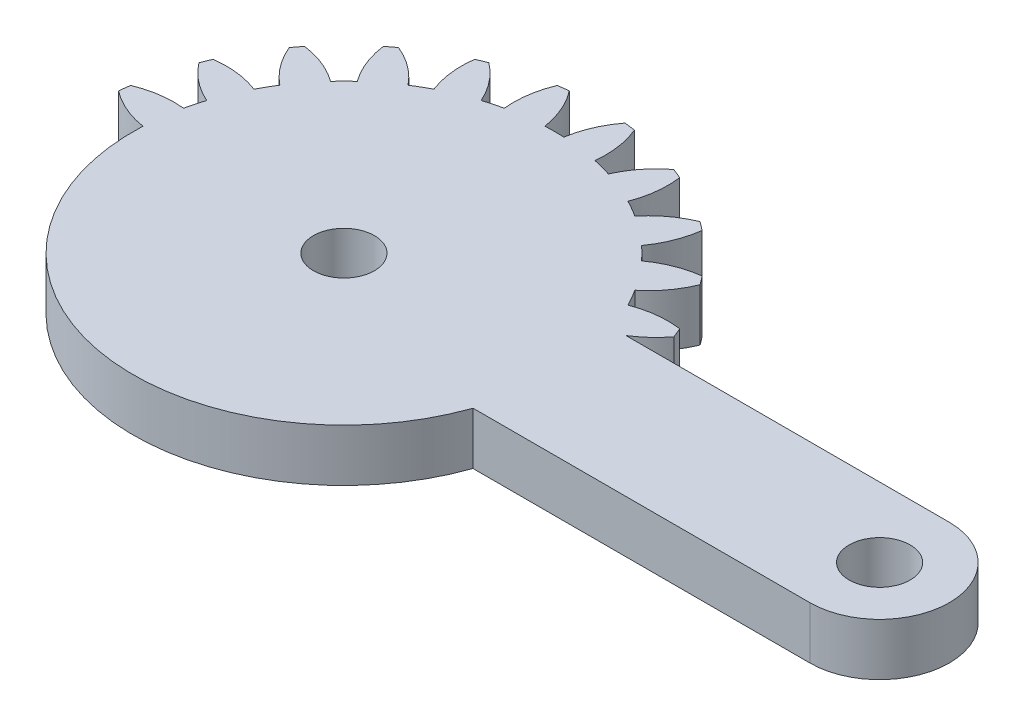
SolidWorks part; units mm, degrees
ref_plane "Front Plane" through (0, 0, 0) normal (0, 0, 1) x (1, 0, 0)
ref_plane "Top Plane" through (0, 0, 0) normal (0, 1, 0) x (1, 0, 0)
ref_plane "Right Plane" through (0, 0, 0) normal (1, 0, 0) x (0, 0, -1)
sketch "Sketch1" plane through (0, 0, 0) normal (0, 1, 0) x (1, 0, 0)
  line L0 (20.6437, 4) -> (2.0816, 4)
  line L1 (2.0816, -4) -> (20.6437, -4)
  arc A0 (2.0816, 4) -> (3.5217, 5.3071) centre (-0.7683, 8.5867) ccw
  arc A1 (3.5217, 5.3071) -> (3.2829, 5.8838) centre (-10.1063, 0) ccw
  arc A2 (3.2829, 5.8838) -> (0.6271, 5.5703) centre (2.5684, 0.5313) ccw
  arc A3 (0.6271, 5.5703) -> (0.0844, 6.5103) centre (-10.1063, 0) ccw
  arc A4 (0.0844, 6.5103) -> (1.6838, 8.6535) centre (-3.3089, 10.711) ccw
  arc A5 (1.6838, 8.6535) -> (1.3038, 9.1487) centre (-10.1063, 0) ccw
  arc A6 (1.3038, 9.1487) -> (-1.1803, 8.1585) centre (1.999, 3.7936) ccw
  arc A7 (-1.1803, 8.1585) -> (-1.9479, 8.926) centre (-10.1063, 0) ccw
  arc A8 (-1.9479, 8.926) -> (-0.9576, 11.4102) centre (-6.3127, 12.1053) ccw
  arc A9 (-0.9576, 11.4102) -> (-1.4528, 11.7901) centre (-10.1063, 0) ccw
  arc A10 (-1.4528, 11.7901) -> (-3.596, 10.1907) centre (0.6046, 6.7975) ccw
  arc A11 (-3.596, 10.1907) -> (-4.5361, 10.7334) centre (-10.1063, 0) ccw
  arc A12 (-4.5361, 10.7334) -> (-4.2225, 13.3892) centre (-9.5751, 12.6747) ccw
  arc A13 (-4.2225, 13.3892) -> (-4.7992, 13.6281) centre (-10.1063, 0) ccw
  arc A14 (-4.7992, 13.6281) -> (-6.4554, 11.5285) centre (-1.5196, 9.3381) ccw
  arc A15 (-6.4554, 11.5285) -> (-7.5039, 11.8094) centre (-10.1063, 0) ccw
  arc A16 (-7.5039, 11.8094) -> (-7.8884, 14.4558) centre (-12.8736, 12.3803) ccw
  arc A17 (-7.8884, 14.4558) -> (-8.5072, 14.5373) centre (-10.1063, 0) ccw
  arc A18 (-8.5072, 14.5373) -> (-9.5636, 12.0806) centre (-4.2291, 11.2423) ccw
  arc A19 (-9.5636, 12.0806) -> (-10.6491, 12.0806) centre (-10.1063, 0) ccw
  arc A20 (-10.6491, 12.0806) -> (-11.7054, 14.5373) centre (-15.9836, 11.2423) ccw
  arc A21 (-11.7054, 14.5373) -> (-12.3243, 14.4558) centre (-10.1063, 0) ccw
  arc A22 (-12.3243, 14.4558) -> (-12.7088, 11.8094) centre (-7.3391, 12.3803) ccw
  arc A23 (-12.7088, 11.8094) -> (-13.7573, 11.5285) centre (-10.1063, 0) ccw
  arc A24 (-13.7573, 11.5285) -> (-15.4135, 13.6281) centre (-18.6931, 9.3381) ccw
  arc A25 (-15.4135, 13.6281) -> (-15.9901, 13.3892) centre (-10.1063, 0) ccw
  arc A26 (-15.9901, 13.3892) -> (-15.6766, 10.7334) centre (-10.6376, 12.6747) ccw
  arc A27 (-15.6766, 10.7334) -> (-16.6166, 10.1907) centre (-10.1063, 0) ccw
  arc A28 (-16.6166, 10.1907) -> (-18.7599, 11.7901) centre (-20.8173, 6.7975) ccw
  arc A29 (-18.7599, 11.7901) -> (-19.255, 11.4102) centre (-10.1063, 0) ccw
  arc A30 (-19.255, 11.4102) -> (-18.2648, 8.926) centre (-13.9, 12.1053) ccw
  arc A31 (-18.2648, 8.926) -> (-19.0324, 8.1585) centre (-10.1063, 0) ccw
  arc A32 (-19.0324, 8.1585) -> (-21.5165, 9.1487) centre (-22.2117, 3.7936) ccw
  arc A33 (-21.5165, 9.1487) -> (-21.8965, 8.6535) centre (-10.1063, 0) ccw
  arc A34 (-21.8965, 8.6535) -> (-20.2971, 6.5103) centre (-16.9038, 10.711) ccw
  arc A35 (-20.2971, 6.5103) -> (-20.8398, 5.5703) centre (-10.1063, 0) ccw
  arc A36 (-20.8398, 5.5703) -> (-23.4956, 5.8838) centre (-22.7811, 0.5313) ccw
  arc A37 (-23.4956, 5.8838) -> (-23.7344, 5.3071) centre (-10.1063, 0) ccw
  arc A38 (-23.7344, 5.3071) -> (-21.6348, 3.6509) centre (-19.4444, 8.5867) ccw
  arc A39 (-21.6348, 3.6509) -> (-21.9157, 2.6025) centre (-10.1063, 0) ccw
  arc A40 (-21.9157, 2.6025) -> (-24.5622, 2.2179) centre (-22.4867, -2.7673) ccw
  arc A41 (-24.5622, 2.2179) -> (-24.6437, 1.5991) centre (-10.1063, 0) ccw
  arc A42 (-24.6437, 1.5991) -> (-22.1869, 0.5427) centre (-21.3486, 5.8773) ccw
  arc A43 (-22.1869, 0.5427) -> (-22.1869, -0.5427) centre (-10.1063, 0) ccw
  arc A44 (-22.1869, -0.5427) -> (-24.6437, -1.5991) centre (-21.3486, -5.8773) ccw
  arc A45 (-24.6437, -1.5991) -> (-24.5622, -2.2179) centre (-10.1063, 0) ccw
  arc A46 (-24.5622, -2.2179) -> (-21.9157, -2.6025) centre (-22.4867, 2.7673) ccw
  arc A47 (-21.9157, -2.6025) -> (-21.6348, -3.6509) centre (-10.1063, 0) ccw
  arc A48 (-21.6348, -3.6509) -> (-23.7344, -5.3071) centre (-19.4444, -8.5867) ccw
  arc A49 (-23.7344, -5.3071) -> (-23.4956, -5.8838) centre (-10.1063, 0) ccw
  arc A50 (-23.4956, -5.8838) -> (-20.8398, -5.5703) centre (-22.7811, -0.5313) ccw
  arc A51 (-20.8398, -5.5703) -> (-20.2971, -6.5103) centre (-10.1063, 0) ccw
  arc A52 (-20.2971, -6.5103) -> (-21.8965, -8.6535) centre (-16.9038, -10.711) ccw
  arc A53 (-21.8965, -8.6535) -> (-21.5165, -9.1487) centre (-10.1063, 0) ccw
  arc A54 (-21.5165, -9.1487) -> (-19.0324, -8.1585) centre (-22.2117, -3.7936) ccw
  arc A55 (-19.0324, -8.1585) -> (-18.2648, -8.926) centre (-10.1063, 0) ccw
  arc A56 (-18.2648, -8.926) -> (-19.255, -11.4102) centre (-13.9, -12.1053) ccw
  arc A57 (-19.255, -11.4102) -> (-18.7599, -11.7901) centre (-10.1063, 0) ccw
  arc A58 (-18.7599, -11.7901) -> (-16.6166, -10.1907) centre (-20.8173, -6.7975) ccw
  arc A59 (-16.6166, -10.1907) -> (-15.6766, -10.7334) centre (-10.1063, 0) ccw
  arc A60 (-15.6766, -10.7334) -> (-15.9901, -13.3892) centre (-10.6376, -12.6747) ccw
  arc A61 (-15.9901, -13.3892) -> (-15.4135, -13.6281) centre (-10.1063, 0) ccw
  arc A62 (-15.4135, -13.6281) -> (-13.7573, -11.5285) centre (-18.6931, -9.3381) ccw
  arc A63 (-13.7573, -11.5285) -> (-12.7088, -11.8094) centre (-10.1063, 0) ccw
  arc A64 (-12.7088, -11.8094) -> (-12.3243, -14.4558) centre (-7.3391, -12.3803) ccw
  arc A65 (-12.3243, -14.4558) -> (-11.7054, -14.5373) centre (-10.1063, 0) ccw
  arc A66 (-11.7054, -14.5373) -> (-10.6491, -12.0806) centre (-15.9836, -11.2423) ccw
  arc A67 (-10.6491, -12.0806) -> (-9.5636, -12.0806) centre (-10.1063, 0) ccw
  arc A68 (-9.5636, -12.0806) -> (-8.5072, -14.5373) centre (-4.2291, -11.2423) ccw
  arc A69 (-8.5072, -14.5373) -> (-7.8884, -14.4558) centre (-10.1063, 0) ccw
  arc A70 (-7.8884, -14.4558) -> (-7.5039, -11.8094) centre (-12.8736, -12.3803) ccw
  arc A71 (-7.5039, -11.8094) -> (-6.4554, -11.5285) centre (-10.1063, 0) ccw
  arc A72 (-6.4554, -11.5285) -> (-4.7992, -13.6281) centre (-1.5196, -9.3381) ccw
  arc A73 (-4.7992, -13.6281) -> (-4.2225, -13.3892) centre (-10.1063, 0) ccw
  arc A74 (-4.2225, -13.3892) -> (-4.5361, -10.7334) centre (-9.5751, -12.6747) ccw
  arc A75 (-4.5361, -10.7334) -> (-3.596, -10.1907) centre (-10.1063, 0) ccw
  arc A76 (-3.596, -10.1907) -> (-1.4528, -11.7901) centre (0.6046, -6.7975) ccw
  arc A77 (-1.4528, -11.7901) -> (-0.9576, -11.4102) centre (-10.1063, 0) ccw
  arc A78 (-0.9576, -11.4102) -> (-1.9479, -8.926) centre (-6.3127, -12.1053) ccw
  arc A79 (-1.9479, -8.926) -> (-1.1803, -8.1585) centre (-10.1063, 0) ccw
  arc A80 (-1.1803, -8.1585) -> (1.3038, -9.1487) centre (1.999, -3.7936) ccw
  arc A81 (1.3038, -9.1487) -> (1.6838, -8.6535) centre (-10.1063, 0) ccw
  arc A82 (1.6838, -8.6535) -> (0.0844, -6.5103) centre (-3.3089, -10.711) ccw
  arc A83 (0.0844, -6.5103) -> (0.6271, -5.5703) centre (-10.1063, 0) ccw
  arc A84 (0.6271, -5.5703) -> (3.2829, -5.8838) centre (2.5684, -0.5313) ccw
  arc A85 (3.2829, -5.8838) -> (3.5217, -5.3071) centre (-10.1063, 0) ccw
  arc A86 (3.5217, -5.3071) -> (2.0816, -4) centre (-0.7683, -8.5867) ccw
  arc A87 (20.6437, -4) -> (20.6437, 4) centre (20.6437, 0) ccw
  circle A88 centre (-10.1063, 0) radius 1.75
  circle A89 centre (20.6437, 0) radius 1.75
  dimension "D1" = 3.5
  dimension "D2" = 3.5
extrude "Boss-Extrude1" add sketch "Sketch1" along normal blind 3
sketch "Sketch2" plane through (0, 3, 0) normal (0, 1, 0) x (1, 0, 0)
  line L0 (2.0816, -4) -> (1.3057, -4)
  line L2 (20.6437, 4) -> (2.0816, 4)
  line L3 (2.0816, -4) -> (20.6437, -4)
  line L4 (20.6437, 4) -> (2.0816, 4)
  line L5 (2.0816, -4) -> (20.6437, -4)
  circle A0 centre (-10.1063, 0) radius 12.0927
  arc A88 (20.6437, -4) -> (20.6437, 4) centre (20.6437, 0) ccw
  arc A89 (2.0816, 4) -> (3.5217, 5.3071) centre (-0.7683, 8.5867) ccw
  arc A90 (3.5217, 5.3071) -> (3.2829, 5.8838) centre (-10.1063, 0) ccw
  arc A91 (3.2829, 5.8838) -> (0.6271, 5.5703) centre (2.5684, 0.5313) ccw
  arc A92 (0.6271, 5.5703) -> (0.0844, 6.5103) centre (-10.1063, 0) ccw
  arc A93 (0.0844, 6.5103) -> (1.6838, 8.6535) centre (-3.3089, 10.711) ccw
  arc A94 (1.6838, 8.6535) -> (1.3038, 9.1487) centre (-10.1063, 0) ccw
  arc A95 (1.3038, 9.1487) -> (-1.1803, 8.1585) centre (1.999, 3.7936) ccw
  arc A96 (-1.1803, 8.1585) -> (-1.9479, 8.926) centre (-10.1063, 0) ccw
  arc A97 (-1.9479, 8.926) -> (-0.9576, 11.4102) centre (-6.3127, 12.1053) ccw
  arc A98 (-0.9576, 11.4102) -> (-1.4528, 11.7901) centre (-10.1063, 0) ccw
  arc A99 (-1.4528, 11.7901) -> (-3.596, 10.1907) centre (0.6046, 6.7975) ccw
  arc A100 (-3.596, 10.1907) -> (-4.5361, 10.7334) centre (-10.1063, 0) ccw
  arc A101 (-4.5361, 10.7334) -> (-4.2225, 13.3892) centre (-9.5751, 12.6747) ccw
  arc A102 (-4.2225, 13.3892) -> (-4.7992, 13.6281) centre (-10.1063, 0) ccw
  arc A103 (-4.7992, 13.6281) -> (-6.4554, 11.5285) centre (-1.5196, 9.3381) ccw
  arc A104 (-6.4554, 11.5285) -> (-7.5039, 11.8094) centre (-10.1063, 0) ccw
  arc A105 (-7.5039, 11.8094) -> (-7.8884, 14.4558) centre (-12.8736, 12.3803) ccw
  arc A106 (-7.8884, 14.4558) -> (-8.5072, 14.5373) centre (-10.1063, 0) ccw
  arc A107 (-8.5072, 14.5373) -> (-9.5636, 12.0806) centre (-4.2291, 11.2423) ccw
  arc A108 (-9.5636, 12.0806) -> (-10.6491, 12.0806) centre (-10.1063, 0) ccw
  arc A109 (-10.6491, 12.0806) -> (-11.7054, 14.5373) centre (-15.9836, 11.2423) ccw
  arc A110 (-11.7054, 14.5373) -> (-12.3243, 14.4558) centre (-10.1063, 0) ccw
  arc A111 (-12.3243, 14.4558) -> (-12.7088, 11.8094) centre (-7.3391, 12.3803) ccw
  arc A112 (-12.7088, 11.8094) -> (-13.7573, 11.5285) centre (-10.1063, 0) ccw
  arc A113 (-13.7573, 11.5285) -> (-15.4135, 13.6281) centre (-18.6931, 9.3381) ccw
  arc A114 (-15.4135, 13.6281) -> (-15.9901, 13.3892) centre (-10.1063, 0) ccw
  arc A115 (-15.9901, 13.3892) -> (-15.6766, 10.7334) centre (-10.6376, 12.6747) ccw
  arc A116 (-15.6766, 10.7334) -> (-16.6166, 10.1907) centre (-10.1063, 0) ccw
  arc A117 (-16.6166, 10.1907) -> (-18.7599, 11.7901) centre (-20.8173, 6.7975) ccw
  arc A118 (-18.7599, 11.7901) -> (-19.255, 11.4102) centre (-10.1063, 0) ccw
  arc A119 (-19.255, 11.4102) -> (-18.2648, 8.926) centre (-13.9, 12.1053) ccw
  arc A120 (-18.2648, 8.926) -> (-19.0324, 8.1585) centre (-10.1063, 0) ccw
  arc A121 (-19.0324, 8.1585) -> (-21.5165, 9.1487) centre (-22.2117, 3.7936) ccw
  arc A122 (-21.5165, 9.1487) -> (-21.8965, 8.6535) centre (-10.1063, 0) ccw
  arc A123 (-21.8965, 8.6535) -> (-20.2971, 6.5103) centre (-16.9038, 10.711) ccw
  arc A124 (-20.2971, 6.5103) -> (-20.8398, 5.5703) centre (-10.1063, 0) ccw
  arc A125 (-20.8398, 5.5703) -> (-23.4956, 5.8838) centre (-22.7811, 0.5313) ccw
  arc A126 (-23.4956, 5.8838) -> (-23.7344, 5.3071) centre (-10.1063, 0) ccw
  arc A127 (-23.7344, 5.3071) -> (-21.6348, 3.6509) centre (-19.4444, 8.5867) ccw
  arc A128 (-21.6348, 3.6509) -> (-21.9157, 2.6025) centre (-10.1063, 0) ccw
  arc A129 (-21.9157, 2.6025) -> (-24.5622, 2.2179) centre (-22.4867, -2.7673) ccw
  arc A130 (-24.5622, 2.2179) -> (-24.6437, 1.5991) centre (-10.1063, 0) ccw
  arc A131 (-24.6437, 1.5991) -> (-22.1869, 0.5427) centre (-21.3486, 5.8773) ccw
  arc A132 (-22.1869, 0.5427) -> (-22.1869, -0.5427) centre (-10.1063, 0) ccw
  arc A133 (-22.1869, -0.5427) -> (-24.6437, -1.5991) centre (-21.3486, -5.8773) ccw
  arc A134 (-24.6437, -1.5991) -> (-24.5622, -2.2179) centre (-10.1063, 0) ccw
  arc A135 (-24.5622, -2.2179) -> (-21.9157, -2.6025) centre (-22.4867, 2.7673) ccw
  arc A136 (-21.9157, -2.6025) -> (-21.6348, -3.6509) centre (-10.1063, 0) ccw
  arc A137 (-21.6348, -3.6509) -> (-23.7344, -5.3071) centre (-19.4444, -8.5867) ccw
  arc A138 (-23.7344, -5.3071) -> (-23.4956, -5.8838) centre (-10.1063, 0) ccw
  arc A139 (-23.4956, -5.8838) -> (-20.8398, -5.5703) centre (-22.7811, -0.5313) ccw
  arc A140 (-20.8398, -5.5703) -> (-20.2971, -6.5103) centre (-10.1063, 0) ccw
  arc A141 (-20.2971, -6.5103) -> (-21.8965, -8.6535) centre (-16.9038, -10.711) ccw
  arc A142 (-21.8965, -8.6535) -> (-21.5165, -9.1487) centre (-10.1063, 0) ccw
  arc A143 (-21.5165, -9.1487) -> (-19.0324, -8.1585) centre (-22.2117, -3.7936) ccw
  arc A144 (-19.0324, -8.1585) -> (-18.2648, -8.926) centre (-10.1063, 0) ccw
  arc A145 (-18.2648, -8.926) -> (-19.255, -11.4102) centre (-13.9, -12.1053) ccw
  arc A146 (-19.255, -11.4102) -> (-18.7599, -11.7901) centre (-10.1063, 0) ccw
  arc A147 (-18.7599, -11.7901) -> (-16.6166, -10.1907) centre (-20.8173, -6.7975) ccw
  arc A148 (-16.6166, -10.1907) -> (-15.6766, -10.7334) centre (-10.1063, 0) ccw
  arc A149 (-15.6766, -10.7334) -> (-15.9901, -13.3892) centre (-10.6376, -12.6747) ccw
  arc A150 (-15.9901, -13.3892) -> (-15.4135, -13.6281) centre (-10.1063, 0) ccw
  arc A151 (-15.4135, -13.6281) -> (-13.7573, -11.5285) centre (-18.6931, -9.3381) ccw
  arc A152 (-13.7573, -11.5285) -> (-12.7088, -11.8094) centre (-10.1063, 0) ccw
  arc A153 (-12.7088, -11.8094) -> (-12.3243, -14.4558) centre (-7.3391, -12.3803) ccw
  arc A154 (-12.3243, -14.4558) -> (-11.7054, -14.5373) centre (-10.1063, 0) ccw
  arc A155 (-11.7054, -14.5373) -> (-10.6491, -12.0806) centre (-15.9836, -11.2423) ccw
  arc A156 (-10.6491, -12.0806) -> (-9.5636, -12.0806) centre (-10.1063, 0) ccw
  arc A157 (-9.5636, -12.0806) -> (-8.5072, -14.5373) centre (-4.2291, -11.2423) ccw
  arc A158 (-8.5072, -14.5373) -> (-7.8884, -14.4558) centre (-10.1063, 0) ccw
  arc A159 (-7.8884, -14.4558) -> (-7.5039, -11.8094) centre (-12.8736, -12.3803) ccw
  arc A160 (-7.5039, -11.8094) -> (-6.4554, -11.5285) centre (-10.1063, 0) ccw
  arc A161 (-6.4554, -11.5285) -> (-4.7992, -13.6281) centre (-1.5196, -9.3381) ccw
  arc A162 (-4.7992, -13.6281) -> (-4.2225, -13.3892) centre (-10.1063, 0) ccw
  arc A163 (-4.2225, -13.3892) -> (-4.5361, -10.7334) centre (-9.5751, -12.6747) ccw
  arc A164 (-4.5361, -10.7334) -> (-3.596, -10.1907) centre (-10.1063, 0) ccw
  arc A165 (-3.596, -10.1907) -> (-1.4528, -11.7901) centre (0.6046, -6.7975) ccw
  arc A166 (-1.4528, -11.7901) -> (-0.9576, -11.4102) centre (-10.1063, 0) ccw
  arc A167 (-0.9576, -11.4102) -> (-1.9479, -8.926) centre (-6.3127, -12.1053) ccw
  arc A168 (-1.9479, -8.926) -> (-1.1803, -8.1585) centre (-10.1063, 0) ccw
  arc A169 (-1.1803, -8.1585) -> (1.3038, -9.1487) centre (1.999, -3.7936) ccw
  arc A170 (1.3038, -9.1487) -> (1.6838, -8.6535) centre (-10.1063, 0) ccw
  arc A171 (1.6838, -8.6535) -> (0.0844, -6.5103) centre (-3.3089, -10.711) ccw
  arc A172 (0.0844, -6.5103) -> (0.6271, -5.5703) centre (-10.1063, 0) ccw
  arc A173 (0.6271, -5.5703) -> (3.2829, -5.8838) centre (2.5684, -0.5313) ccw
  arc A174 (3.2829, -5.8838) -> (3.5217, -5.3071) centre (-10.1063, 0) ccw
  arc A175 (3.5217, -5.3071) -> (2.0816, -4) centre (-0.7683, -8.5867) ccw
  arc A176 (20.6437, -4) -> (20.6437, 4) centre (20.6437, 0) ccw
  arc A177 (2.0816, 4) -> (3.5217, 5.3071) centre (-0.7683, 8.5867) ccw
  arc A178 (3.5217, 5.3071) -> (3.2829, 5.8838) centre (-10.1063, 0) ccw
  arc A179 (3.2829, 5.8838) -> (0.6271, 5.5703) centre (2.5684, 0.5313) ccw
  arc A180 (0.6271, 5.5703) -> (0.0844, 6.5103) centre (-10.1063, 0) ccw
  arc A181 (0.0844, 6.5103) -> (1.6838, 8.6535) centre (-3.3089, 10.711) ccw
  arc A182 (1.6838, 8.6535) -> (1.3038, 9.1487) centre (-10.1063, 0) ccw
  arc A183 (1.3038, 9.1487) -> (-1.1803, 8.1585) centre (1.999, 3.7936) ccw
  arc A184 (-1.1803, 8.1585) -> (-1.9479, 8.926) centre (-10.1063, 0) ccw
  arc A185 (-1.9479, 8.926) -> (-0.9576, 11.4102) centre (-6.3127, 12.1053) ccw
  arc A186 (-0.9576, 11.4102) -> (-1.4528, 11.7901) centre (-10.1063, 0) ccw
  arc A187 (-1.4528, 11.7901) -> (-3.596, 10.1907) centre (0.6046, 6.7975) ccw
  arc A188 (-3.596, 10.1907) -> (-4.5361, 10.7334) centre (-10.1063, 0) ccw
  arc A189 (-4.5361, 10.7334) -> (-4.2225, 13.3892) centre (-9.5751, 12.6747) ccw
  arc A190 (-4.2225, 13.3892) -> (-4.7992, 13.6281) centre (-10.1063, 0) ccw
  arc A191 (-4.7992, 13.6281) -> (-6.4554, 11.5285) centre (-1.5196, 9.3381) ccw
  arc A192 (-6.4554, 11.5285) -> (-7.5039, 11.8094) centre (-10.1063, 0) ccw
  arc A193 (-7.5039, 11.8094) -> (-7.8884, 14.4558) centre (-12.8736, 12.3803) ccw
  arc A194 (-7.8884, 14.4558) -> (-8.5072, 14.5373) centre (-10.1063, 0) ccw
  arc A195 (-8.5072, 14.5373) -> (-9.5636, 12.0806) centre (-4.2291, 11.2423) ccw
  arc A196 (-9.5636, 12.0806) -> (-10.6491, 12.0806) centre (-10.1063, 0) ccw
  arc A197 (-10.6491, 12.0806) -> (-11.7054, 14.5373) centre (-15.9836, 11.2423) ccw
  arc A198 (-11.7054, 14.5373) -> (-12.3243, 14.4558) centre (-10.1063, 0) ccw
  arc A199 (-12.3243, 14.4558) -> (-12.7088, 11.8094) centre (-7.3391, 12.3803) ccw
  arc A200 (-12.7088, 11.8094) -> (-13.7573, 11.5285) centre (-10.1063, 0) ccw
  arc A201 (-13.7573, 11.5285) -> (-15.4135, 13.6281) centre (-18.6931, 9.3381) ccw
  arc A202 (-15.4135, 13.6281) -> (-15.9901, 13.3892) centre (-10.1063, 0) ccw
  arc A203 (-15.9901, 13.3892) -> (-15.6766, 10.7334) centre (-10.6376, 12.6747) ccw
  arc A204 (-15.6766, 10.7334) -> (-16.6166, 10.1907) centre (-10.1063, 0) ccw
  arc A205 (-16.6166, 10.1907) -> (-18.7599, 11.7901) centre (-20.8173, 6.7975) ccw
  arc A206 (-18.7599, 11.7901) -> (-19.255, 11.4102) centre (-10.1063, 0) ccw
  arc A207 (-19.255, 11.4102) -> (-18.2648, 8.926) centre (-13.9, 12.1053) ccw
  arc A208 (-18.2648, 8.926) -> (-19.0324, 8.1585) centre (-10.1063, 0) ccw
  arc A209 (-19.0324, 8.1585) -> (-21.5165, 9.1487) centre (-22.2117, 3.7936) ccw
  arc A210 (-21.5165, 9.1487) -> (-21.8965, 8.6535) centre (-10.1063, 0) ccw
  arc A211 (-21.8965, 8.6535) -> (-20.2971, 6.5103) centre (-16.9038, 10.711) ccw
  arc A212 (-20.2971, 6.5103) -> (-20.8398, 5.5703) centre (-10.1063, 0) ccw
  arc A213 (-20.8398, 5.5703) -> (-23.4956, 5.8838) centre (-22.7811, 0.5313) ccw
  arc A214 (-23.4956, 5.8838) -> (-23.7344, 5.3071) centre (-10.1063, 0) ccw
  arc A215 (-23.7344, 5.3071) -> (-21.6348, 3.6509) centre (-19.4444, 8.5867) ccw
  arc A216 (-21.6348, 3.6509) -> (-21.9157, 2.6025) centre (-10.1063, 0) ccw
  arc A217 (-21.9157, 2.6025) -> (-24.5622, 2.2179) centre (-22.4867, -2.7673) ccw
  arc A218 (-24.5622, 2.2179) -> (-24.6437, 1.5991) centre (-10.1063, 0) ccw
  arc A219 (-24.6437, 1.5991) -> (-22.1869, 0.5427) centre (-21.3486, 5.8773) ccw
  arc A220 (-22.1869, 0.5427) -> (-22.1869, -0.5427) centre (-10.1063, 0) ccw
  arc A221 (-22.1869, -0.5427) -> (-24.6437, -1.5991) centre (-21.3486, -5.8773) ccw
  arc A222 (-24.6437, -1.5991) -> (-24.5622, -2.2179) centre (-10.1063, 0) ccw
  arc A223 (-24.5622, -2.2179) -> (-21.9157, -2.6025) centre (-22.4867, 2.7673) ccw
  arc A224 (-21.9157, -2.6025) -> (-21.6348, -3.6509) centre (-10.1063, 0) ccw
  arc A225 (-21.6348, -3.6509) -> (-23.7344, -5.3071) centre (-19.4444, -8.5867) ccw
  arc A226 (-23.7344, -5.3071) -> (-23.4956, -5.8838) centre (-10.1063, 0) ccw
  arc A227 (-23.4956, -5.8838) -> (-20.8398, -5.5703) centre (-22.7811, -0.5313) ccw
  arc A228 (-20.8398, -5.5703) -> (-20.2971, -6.5103) centre (-10.1063, 0) ccw
  arc A229 (-20.2971, -6.5103) -> (-21.8965, -8.6535) centre (-16.9038, -10.711) ccw
  arc A230 (-21.8965, -8.6535) -> (-21.5165, -9.1487) centre (-10.1063, 0) ccw
  arc A231 (-21.5165, -9.1487) -> (-19.0324, -8.1585) centre (-22.2117, -3.7936) ccw
  arc A232 (-19.0324, -8.1585) -> (-18.2648, -8.926) centre (-10.1063, 0) ccw
  arc A233 (-18.2648, -8.926) -> (-19.255, -11.4102) centre (-13.9, -12.1053) ccw
  arc A234 (-19.255, -11.4102) -> (-18.7599, -11.7901) centre (-10.1063, 0) ccw
  arc A235 (-18.7599, -11.7901) -> (-16.6166, -10.1907) centre (-20.8173, -6.7975) ccw
  arc A236 (-16.6166, -10.1907) -> (-15.6766, -10.7334) centre (-10.1063, 0) ccw
  arc A237 (-15.6766, -10.7334) -> (-15.9901, -13.3892) centre (-10.6376, -12.6747) ccw
  arc A238 (-15.9901, -13.3892) -> (-15.4135, -13.6281) centre (-10.1063, 0) ccw
  arc A239 (-15.4135, -13.6281) -> (-13.7573, -11.5285) centre (-18.6931, -9.3381) ccw
  arc A240 (-13.7573, -11.5285) -> (-12.7088, -11.8094) centre (-10.1063, 0) ccw
  arc A241 (-12.7088, -11.8094) -> (-12.3243, -14.4558) centre (-7.3391, -12.3803) ccw
  arc A242 (-12.3243, -14.4558) -> (-11.7054, -14.5373) centre (-10.1063, 0) ccw
  arc A243 (-11.7054, -14.5373) -> (-10.6491, -12.0806) centre (-15.9836, -11.2423) ccw
  arc A244 (-10.6491, -12.0806) -> (-9.5636, -12.0806) centre (-10.1063, 0) ccw
  arc A245 (-9.5636, -12.0806) -> (-8.5072, -14.5373) centre (-4.2291, -11.2423) ccw
  arc A246 (-8.5072, -14.5373) -> (-7.8884, -14.4558) centre (-10.1063, 0) ccw
  arc A247 (-7.8884, -14.4558) -> (-7.5039, -11.8094) centre (-12.8736, -12.3803) ccw
  arc A248 (-7.5039, -11.8094) -> (-6.4554, -11.5285) centre (-10.1063, 0) ccw
  arc A249 (-6.4554, -11.5285) -> (-4.7992, -13.6281) centre (-1.5196, -9.3381) ccw
  arc A250 (-4.7992, -13.6281) -> (-4.2225, -13.3892) centre (-10.1063, 0) ccw
  arc A251 (-4.2225, -13.3892) -> (-4.5361, -10.7334) centre (-9.5751, -12.6747) ccw
  arc A252 (-4.5361, -10.7334) -> (-3.596, -10.1907) centre (-10.1063, 0) ccw
  arc A253 (-3.596, -10.1907) -> (-1.4528, -11.7901) centre (0.6046, -6.7975) ccw
  arc A254 (-1.4528, -11.7901) -> (-0.9576, -11.4102) centre (-10.1063, 0) ccw
  arc A255 (-0.9576, -11.4102) -> (-1.9479, -8.926) centre (-6.3127, -12.1053) ccw
  arc A256 (-1.9479, -8.926) -> (-1.1803, -8.1585) centre (-10.1063, 0) ccw
  arc A257 (-1.1803, -8.1585) -> (1.3038, -9.1487) centre (1.999, -3.7936) ccw
  arc A258 (1.3038, -9.1487) -> (1.6838, -8.6535) centre (-10.1063, 0) ccw
  arc A259 (1.6838, -8.6535) -> (0.0844, -6.5103) centre (-3.3089, -10.711) ccw
  arc A260 (0.0844, -6.5103) -> (0.6271, -5.5703) centre (-10.1063, 0) ccw
  arc A261 (0.6271, -5.5703) -> (3.2829, -5.8838) centre (2.5684, -0.5313) ccw
  arc A262 (3.2829, -5.8838) -> (3.5217, -5.3071) centre (-10.1063, 0) ccw
  arc A263 (3.5217, -5.3071) -> (2.0816, -4) centre (-0.7683, -8.5867) ccw
  dimension "D1" = 0
extrude "Cut-Extrude1" cut sketch "Sketch2" against normal blind 10 contours A222 A223 A0 A221 | A226 A227 A0 A225 | A230 A231 A0 A229 | A234 A235 A0 A233 | A238 A239 A0 A237 | A242 A243 A0 A241 | A246 A247 A0 A245 | A250 A251 A0 A249 | A254 A255 A0 A253 | A258 A259 A0 A257 | A262 A263 L0 A0 A261 region at (2.066, 3, 5.0775) region at (0.3325, 3, 8.01) region at (-2.0963, 3, 10.4389) region at (-5.071, 3, 12.1563) region at (-8.3889, 3, 13.0454) region at (-11.8238, 3, 13.0454) region at (-15.1417, 3, 12.1563) region at (-18.1164, 3, 10.4389) region at (-20.5452, 3, 8.01) region at (-22.2627, 3, 5.0353) region at (-23.1517, 3, 1.7175)
